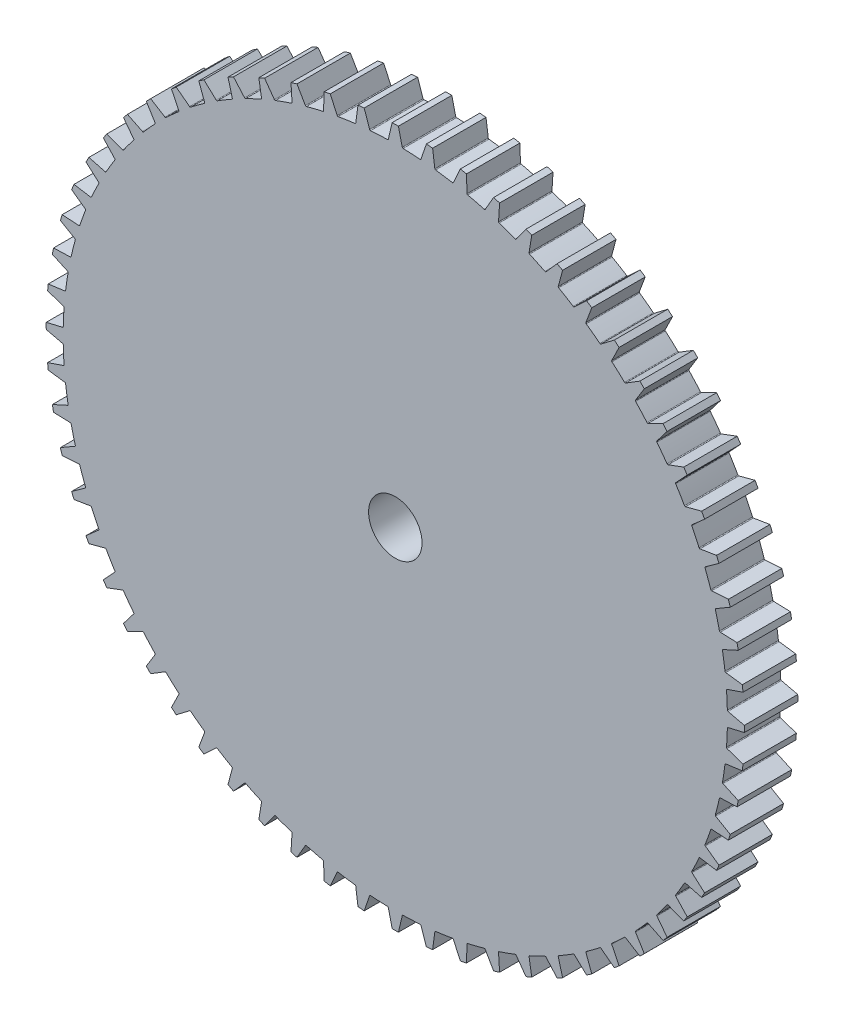
SolidWorks part; units mm, degrees
material "AISI 4340 Steel, annealed"
ref_plane "Front Plane" through (0, 0, 0) normal (0, 0, 1) x (1, 0, 0)
ref_plane "Top Plane" through (0, 0, 0) normal (0, 1, 0) x (1, 0, 0)
ref_plane "Right Plane" through (0, 0, 0) normal (1, 0, 0) x (0, 0, -1)
sketch "Sketch1" plane through (0, 0, 0) normal (0, 0, 1) x (1, 0, 0)
  circle A0 centre (0, 0) radius 186.5
  dimension "D1" = 373
extrude "Boss-Extrude1" add sketch "Sketch1" along normal mid plane 30
sketch "Sketch2" plane through (0, 0, 15) normal (0, 0, 1) x (1, 0, 0)
  line L0 (0, 0) -> (0, 196) construction
  line L1 (1.75, 196.0078) -> (-1.75, 195.9922)
  line L2 (-1.75, 195.9922) -> (-4, 186.4571)
  line L3 (1.75, 196.0078) -> (4, 186.4571)
  circle A0 centre (0, 0) radius 196 construction
  circle A1 centre (0, 0) radius 186.5 construction
  arc A2 (4, 186.4571) -> (-4, 186.4571) centre (0, 0) ccw
  point P7 (0, 196)
  dimension "D1" = 392
  dimension "D2" = 3.5
  dimension "D3" = 8
  dimension "D4" = 4
extrude "Boss-Extrude2" add sketch "Sketch2" against normal blind 30
fillet "Fillet1" radius 0.5 1 edges at (4, 186.4571, 0)
fillet "Fillet2" radius 0.5 1 edges at (-4, 186.4571, 0)
pattern_circular "CirPattern1" count 64 over 360 about axis through (0, 0, 15) along (0, 0, 1) of "Fillet2", "Fillet1", "Boss-Extrude2"
sketch "Sketch3" plane through (0, 0, -15) normal (0, 0, -1) x (-1, 0, 0)
  line L0 (0, 0) -> (0, 20) construction
  line L1 (0, 20) -> (5, 20)
  line L2 (5, 20) -> (5, 14.1421)
  line L3 (0, 20) -> (-5, 20)
  line L4 (-5, 20) -> (-5, 14.1421)
  circle A0 centre (0, 0) radius 44.5
  arc A1 (-5, 14.1421) -> (5, 14.1421) centre (0, 0) ccw
  point P4 (0, 15)
  dimension "D1" = 30
  dimension "D2" = 89
  dimension "D3" = 5
  dimension "D4" = 5
  dimension "D5" = 5
extrude "Boss-Extrude3" add sketch "Sketch3" along normal blind 30
sketch "Sketch4" plane through (0, 0, -15) normal (0, 0, -1) x (-1, 0, 0)
  circle A0 centre (0, 0) radius 15
  dimension "D1" = 30
extrude "Cut-Extrude1" cut sketch "Sketch4" against normal blind 112
